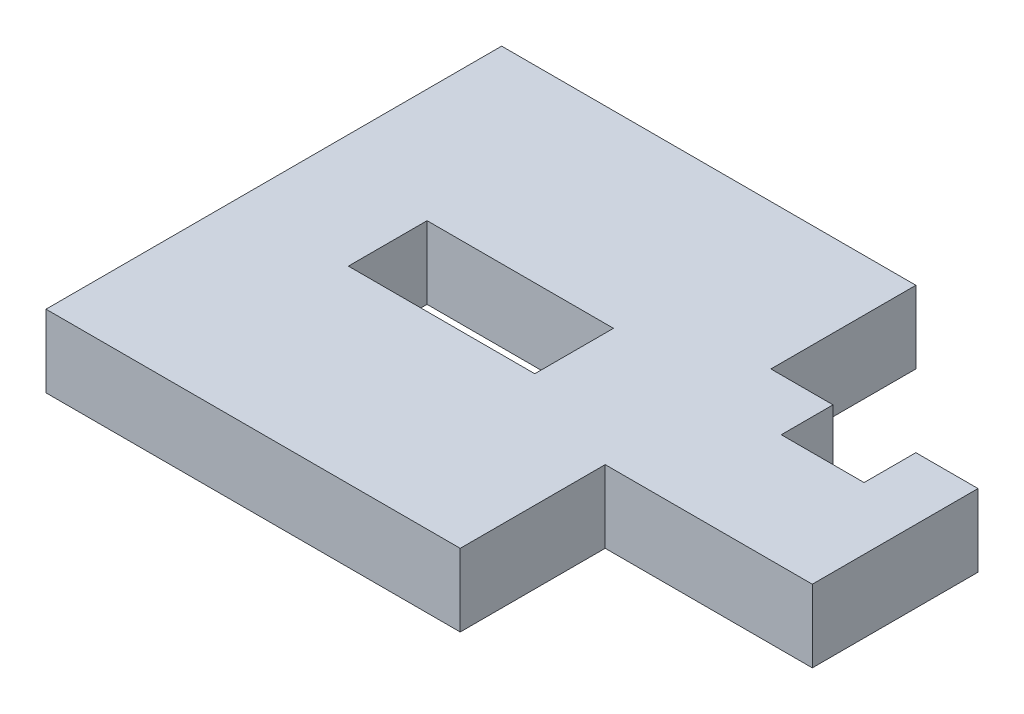
SolidWorks part; units mm, degrees
ref_plane "Front Plane" through (0, 0, 0) normal (0, 0, 1) x (1, 0, 0)
ref_plane "Top Plane" through (0, 0, 0) normal (0, 1, 0) x (1, 0, 0)
ref_plane "Right Plane" through (0, 0, 0) normal (1, 0, 0) x (0, 0, -1)
sketch "Sketch1" plane through (0, 0, 0) normal (0, 1, 0) x (1, 0, 0)
  line L1 (-10, 11) -> (10, 11)
  line L2 (-10, 11) -> (-10, -11)
  line L3 (-10, -11) -> (10, -11)
  line L4 (10, 11) -> (10, -11)
  line L6 (4.5, -1.9) -> (-4.5, -1.9)
  line L7 (4.5, -1.9) -> (4.5, 1.9)
  line L8 (4.5, 1.9) -> (-4.5, 1.9)
  line L9 (-4.5, -1.9) -> (-4.5, 1.9)
  point P4 (0, 1.9)
  point P10 (0, 11)
  point P11 (-4.5, 0)
  point P12 (-10, 0)
  dimension "D1" = 9
  dimension "D2" = 3.8
  dimension "D3" = 20
  dimension "D4" = 22
extrude "Boss-Extrude1" add sketch "Sketch1" along normal blind 4
sketch "Sketch2" plane through (0, 0, 0) normal (0, 1, 0) x (1, 0, 0)
  line L0 (10, 4) -> (20, 4)
  line L1 (10, -11) -> (10, 11) construction
  line L2 (20, 4) -> (20, -4)
  line L3 (20, -4) -> (10, -4)
  line L4 (10, 4) -> (10, -4)
  point P6 (10, 0)
  point P7 (20, 0)
  dimension "D1" = 8
  dimension "D2" = 10
extrude "Boss-Extrude3" add sketch "Sketch2" along normal blind 4
sketch "Sketch3" plane through (0, 0, 0) normal (0, 1, 0) x (1, 0, 0)
  line L0 (10, 4) -> (10, 11) construction
  line L1 (13, 4) -> (17, 4)
  line L2 (13, 4) -> (13, 1.5)
  line L3 (13, 1.5) -> (17, 1.5)
  line L4 (17, 4) -> (17, 1.5)
  dimension "D1" = 4
  dimension "D2" = 2.5
  dimension "D3" = 3
extrude "Cut-Extrude1" cut sketch "Sketch3" along normal through all
chamfer "Chamfer1" distance 0.5 angle 45 16 edges at (0, 0, -11) (-10, 0, 0) (0, 0, 11) (10, 0, 7.5) (15, 0, 4) (20, 0, 0) (18.5, 0, -4) (17, 0, -2.75) (15, 0, -1.5) (10, 0, -7.5) (0, 0, 1.9) (-4.5, 0, 0) (0, 0, -1.9) (4.5, 0, 0) (11.5, 0, -4) (13, 0, -2.75)
